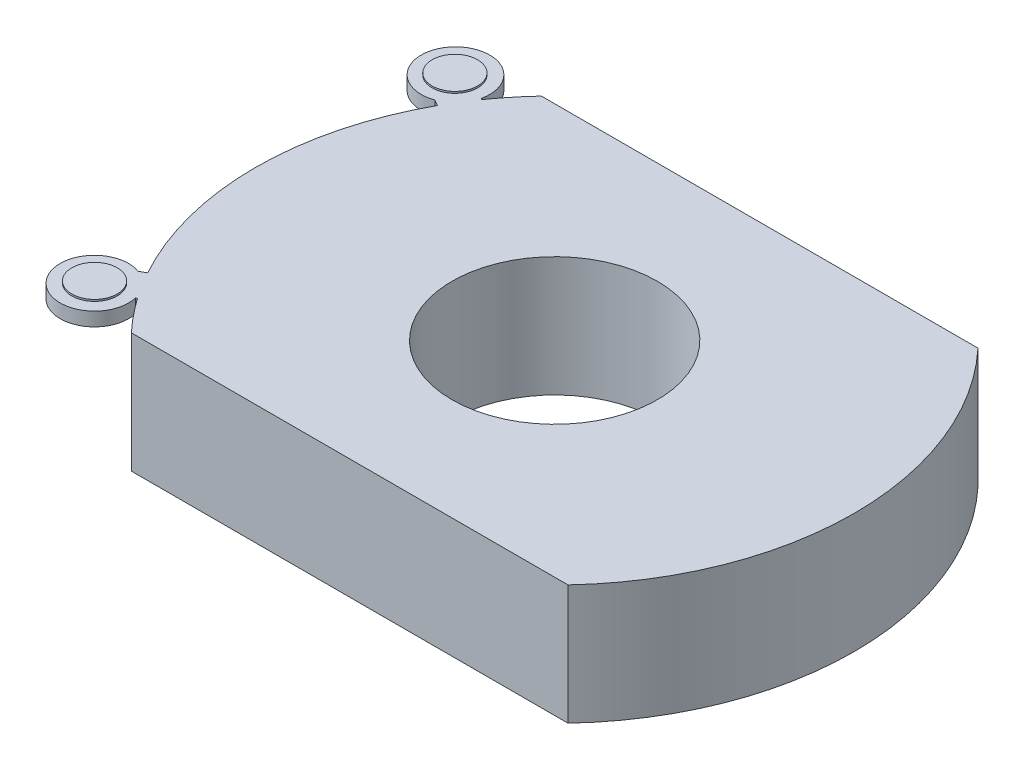
SolidWorks part; units mm, degrees
material "1345 Alloy"
ref_plane "Front Plane" through (0, 0, 0) normal (0, 0, 1) x (1, 0, 0)
ref_plane "Top Plane" through (0, 0, 0) normal (0, 1, 0) x (1, 0, 0)
ref_plane "Right Plane" through (0, 0, 0) normal (1, 0, 0) x (0, 0, -1)
sketch "Sketch1" plane through (0, 0, 0) normal (0, 1, 0) x (1, 0, 0)
  line L0 (-1712.4333, 578.2677) -> (-1658.0172, 559.892) construction
  line L1 (-1682.6566, 611.2885) -> (-1644.8226, 597.5438) construction
  line L2 (-1769.951, 660.0706) -> (-1712.4333, 741.8735) construction
  circle A0 centre (0, 0) radius 1750
  arc A3 (-1712.4333, 578.2677) -> (-1712.4333, 741.8735) centre (-1769.951, 660.0706) cw construction
  arc A4 (-1712.4333, 741.8735) -> (-1682.6566, 611.2885) centre (-1769.951, 660.0706) cw construction
extrude "Boss-Extrude1" add sketch "Sketch1" along normal blind 700
sketch "Sketch9" plane through (0, 0, 0) normal (0, -1, 0) x (1, 0, 0)
  line L1 (-2106.3119, -1198.0599) -> (2106.3119, -1198.0599)
  line L2 (-2106.3119, -1198.0599) -> (-2106.3119, 1198.0599)
  line L3 (-2106.3119, 1198.0599) -> (2106.3119, 1198.0599)
  line L4 (2106.3119, -1198.0599) -> (2106.3119, 1198.0599)
  line L5 (-2106.3119, -1198.0599) -> (2106.3119, 1198.0599) construction
  line L6 (-2106.3119, 1198.0599) -> (2106.3119, -1198.0599) construction
  line L7 (-2636.6179, -2082.9122) -> (2636.6179, -2082.9122)
  line L8 (-2636.6179, -2082.9122) -> (-2636.6179, 2082.9122)
  line L9 (-2636.6179, 2082.9122) -> (2636.6179, 2082.9122)
  line L10 (2636.6179, -2082.9122) -> (2636.6179, 2082.9122)
  line L11 (-2636.6179, -2082.9122) -> (2636.6179, 2082.9122) construction
  line L12 (-2636.6179, 2082.9122) -> (2636.6179, -2082.9122) construction
  point P0 (0, 0)
  point P6 (0, 0)
extrude "Cut-Extrude10" cut sketch "Sketch9" against normal through all both and the other way through all
sketch "Sketch3" plane through (0, 0, 0) normal (0, -1, 0) x (1, 0, 0)
  circle A0 centre (0, 0) radius 600
extrude "Cut-Extrude3" cut sketch "Sketch3" against normal through all both and the other way through all
shell "Shell1" thickness 1.5 removed face at (0, 0, 600)
sketch "Sketch12" plane through (0, 700, 0) normal (0, 1, 0) x (1, 0, 0)
  line L0 (-1432.0962, -1005.7836) -> (-1439.5944, -1011.0497)
  line L1 (-1432.0962, -1005.7836) -> (-1439.5944, -1011.0497)
  line L2 (-1567.0537, -866.7535) -> (-1531.3623, -847.0122)
  line L3 (-1212.6439, -1163.1539) -> (-1531.3623, -847.0122) construction
  line L4 (-1212.6439, 1163.1539) -> (-1531.3623, 847.0122) construction
  line L5 (-1567.0537, 866.7535) -> (-1531.3623, 847.0122)
  line L6 (-1275.5989, 1198.0599) -> (1275.5989, -1198.0599) construction
  line L7 (0, 0) -> (-1750, 0) construction
  line L8 (-1432.0962, 1005.7836) -> (-1439.5944, 1011.0497)
  line L9 (-1432.0962, 1005.7836) -> (-1439.5944, 1011.0497)
  line L13 (0, 0) -> (0, 1750) construction
  line L14 (1212.6439, 1163.1539) -> (1394.7434, 1056.9725) construction
  line L15 (1533.0685, 1076.2848) -> (1275.8583, 1198.0599) construction
  line L16 (1432.0962, 1005.7836) -> (1533.0685, 1076.2848)
  line L17 (1432.0962, 1005.7836) -> (1533.0685, 1076.2848)
  line L18 (1456.8867, 1104.0663) -> (1394.7434, 1056.9725)
  arc A0 (-1275.5989, -1198.0599) -> (-1531.3623, -847.0122) centre (0, 0) cw
  arc A1 (-1432.0962, 1005.7836) -> (-1275.5989, 1198.0599) centre (0, 0) ccw construction
  arc A2 (-1439.5944, -1011.0497) -> (-1567.0537, -866.7535) centre (-1634.7144, -1054.9609) cw
  arc A3 (-1432.0962, -1005.7836) -> (-1275.5989, -1198.0599) centre (0, 0) cw construction
  arc A4 (1275.8583, 1198.0599) -> (1394.7434, 1056.9725) centre (24.3381, 22.854) cw
  arc A5 (-1439.5944, 1011.0497) -> (-1567.0537, 866.7535) centre (-1634.7144, 1054.9609) ccw
  arc A6 (1533.0685, 1076.2848) -> (1456.8867, 1104.0663) centre (1562.0755, 1274.1701) cw
  arc A7 (-1275.5989, 1198.0599) -> (-1531.3623, 847.0122) centre (0, 0) ccw
  arc M6 (-1275.5989, 1198.0599) -> (-1275.5989, -1198.0599) centre (0, 0) ccw
extrude "Boss-Extrude2" add sketch "Sketch12" against normal blind 80 contours A2 L0 L2 M6 | L8 A5 L5 M6 region at (-1633.7874, 700, -1053.2699) region at (-1633.7874, 700, 1053.2699)
sketch "Sketch14" plane through (0, 700, 0) normal (0, 1, 0) x (1, 0, 0)
  line L0 (0, 0) -> (-3568.6491, 0) construction
  circle A0 centre (-1636.0595, -1052.8306) radius 132.8125
  circle A1 centre (-1636.0595, 1052.8306) radius 132.8125
extrude "Boss-Extrude5" add sketch "Sketch14" along normal blind 10
sketch "Sketch18" plane through (0, 698.5, 0) normal (0, -1, 0) x (1, 0, 0)
  line L0 (0, 0) -> (-1178.7098, 0) construction
  line L6 (-1278.7098, -100) -> (-1078.7098, -100)
  line L7 (-1278.7098, -100) -> (-1278.7098, 100)
  line L8 (-1278.7098, 100) -> (-1078.7098, 100)
  line L9 (-1078.7098, -100) -> (-1078.7098, 100)
  line L10 (-1278.7098, -100) -> (-1078.7098, 100) construction
  line L11 (-1278.7098, 100) -> (-1078.7098, -100) construction
  circle A0 centre (-1178.7098, 0) radius 27.5
extrude "Boss-Extrude6" add sketch "Sketch18" along normal blind 50
